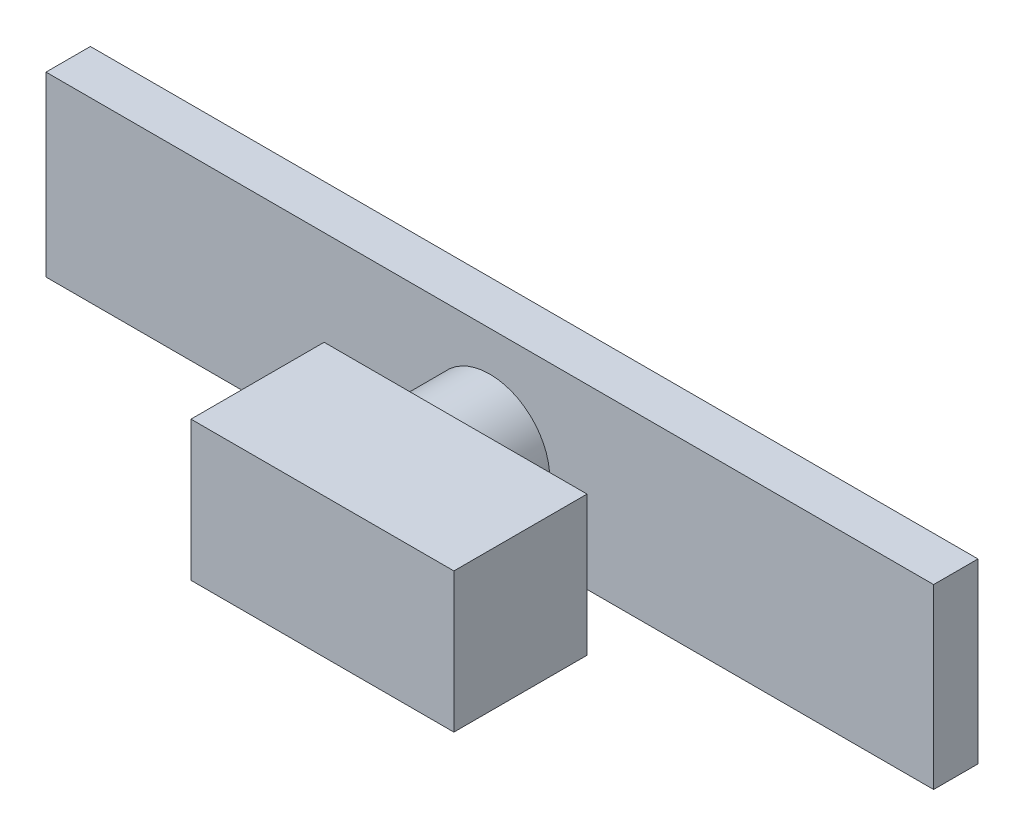
SolidWorks part; units mm, degrees
ref_plane "Front Plane" through (0, 0, 0) normal (0, 0, 1) x (1, 0, 0)
ref_plane "Top Plane" through (0, 0, 0) normal (0, 1, 0) x (1, 0, 0)
ref_plane "Right Plane" through (0, 0, 0) normal (1, 0, 0) x (0, 0, -1)
sketch "Sketch2" plane through (0, 0, 0) normal (0, 0, 1) x (1, 0, 0)
  line L1 (-47.8692, 21.2481) -> (206.1308, 21.2481)
  line L2 (-47.8692, 21.2481) -> (-47.8692, 8.5481)
  line L3 (-47.8692, 8.5481) -> (206.1308, 8.5481)
  line L4 (206.1308, 21.2481) -> (206.1308, 8.5481)
  dimension "D1" = 12.7
  dimension "D2" = 254
extrude "Boss-Extrude1" add sketch "Sketch2" along normal blind 50.8
sketch "Sketch3" plane through (0, 21.2481, 0) normal (0, 1, 0) x (1, 0, 0)
  circle A0 centre (79.1308, -28.4831) radius 17.1408
extrude "Boss-Extrude2" add sketch "Sketch3" along normal blind 19.05
sketch "Sketch4" plane through (0, 40.2981, 0) normal (0, 1, 0) x (1, 0, 0)
  line L1 (50.7675, -8.111) -> (126.0034, -8.111)
  line L2 (50.7675, -8.111) -> (50.7675, -48.0661)
  line L3 (50.7675, -48.0661) -> (126.0034, -48.0661)
  line L4 (126.0034, -8.111) -> (126.0034, -48.0661)
extrude "Boss-Extrude3" add sketch "Sketch4" along normal blind 38.1
scale "Scale2" scale about centroid uniform scaling yes scale factor 0.06
move or copy body "rotate" bodies to move or copy 105 copy no rotation origin (0, 33.6669, 26.5501) rotation axis (1, 0, 0) rotation angle 90
scale "Scale5" scale about centroid uniform scaling yes scale factor 0.25
move or copy body "-4 x" bodies to move or copy 111 copy no translate (-101.6, 0, 0)
move or copy body "-2 y" bodies to move or copy 117 copy no translate (0, -50.8, 0)
scale "Scale6" bodies to scale 121 scale about centroid uniform scaling yes scale factor 0.25
move or copy body "-2.1z" bodies to move or copy 122 copy no translate (0, 0, -53.34)
